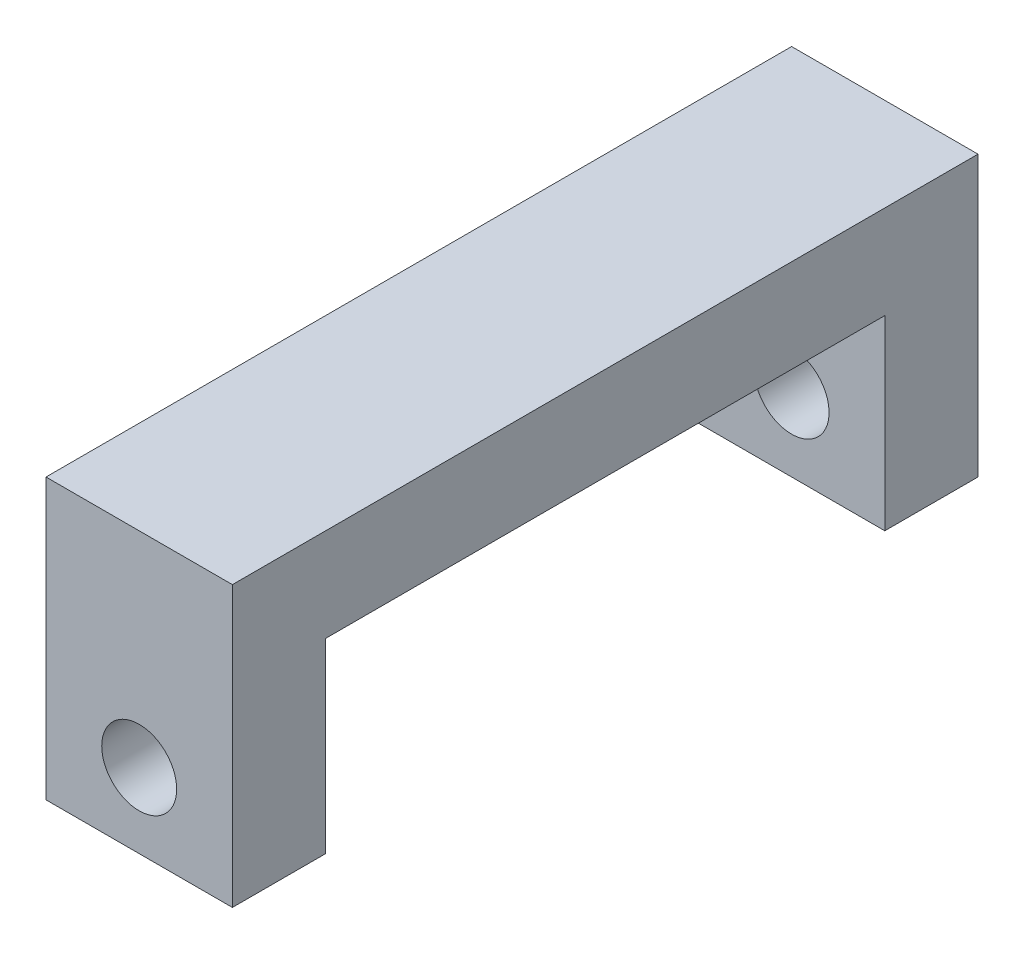
SolidWorks part; units mm, degrees
ref_plane "Front Plane" through (0, 0, 0) normal (0, 0, 1) x (1, 0, 0)
ref_plane "Top Plane" through (0, 0, 0) normal (0, 1, 0) x (1, 0, 0)
ref_plane "Right Plane" through (0, 0, 0) normal (1, 0, 0) x (0, 0, -1)
sketch "Sketch1" plane through (0, 0, 0) normal (1, 0, 0) x (0, 0, -1)
  line L0 (25.4, 0) -> (-25.4, 0)
  line L1 (-25.4, 0) -> (-25.4, -19.05)
  line L2 (-25.4, -19.05) -> (-19.05, -19.05)
  line L3 (-19.05, -19.05) -> (-19.05, -6.35)
  line L4 (-19.05, -6.35) -> (19.05, -6.35)
  line L5 (0, -6.35) -> (0, 49993.65) construction
  line L6 (19.05, -19.05) -> (19.05, -6.35)
  line L7 (25.4, -19.05) -> (19.05, -19.05)
  line L8 (25.4, 0) -> (25.4, -19.05)
  point P11 (0, -6.35)
  point P12 (0, 0)
  dimension "D1" = 6.35
  dimension "D2" = 6.35
  dimension "D3" = 12.7
  dimension "D4" = 19.05
extrude "Boss-Extrude1" add sketch "Sketch1" along normal blind 12.7
hole_wizard "Tap Drill for 1/4-20 Tap1" positions "3DSketch2" profile "Sketch4" hole size "1/4-20" standard "ANSI Inch" end condition through all
sketch3d "3DSketch2"
  line L0 (12.7, -19.05, -25.4) -> (12.7, 0, -25.4) construction
  line L1 (12.7, -19.05, -25.4) -> (0, -19.05, -25.4) construction
  point P0 (6.35, -13.97, -25.4)
  dimension "D1" = 6.35
  dimension "D2" = 5.08
sketch "Sketch4" plane through (6.35, -13.97, -25.4) normal (1, 0, 0) x (0, 1, 0)
  line L0 (0, 0) -> (0, 50.8)
  line L1 (0, 50.8) -> (2.5527, 50.8)
  line L2 (2.5527, 50.8) -> (2.5527, 0)
  line L5 (2.5527, 0) -> (0, 0)
  line L11 (0, -6.35) -> (0, 107.95) construction
  dimension "Thru Hole Dia." = 5.1054
  dimension "Thru Hole Depth" = 50.8
